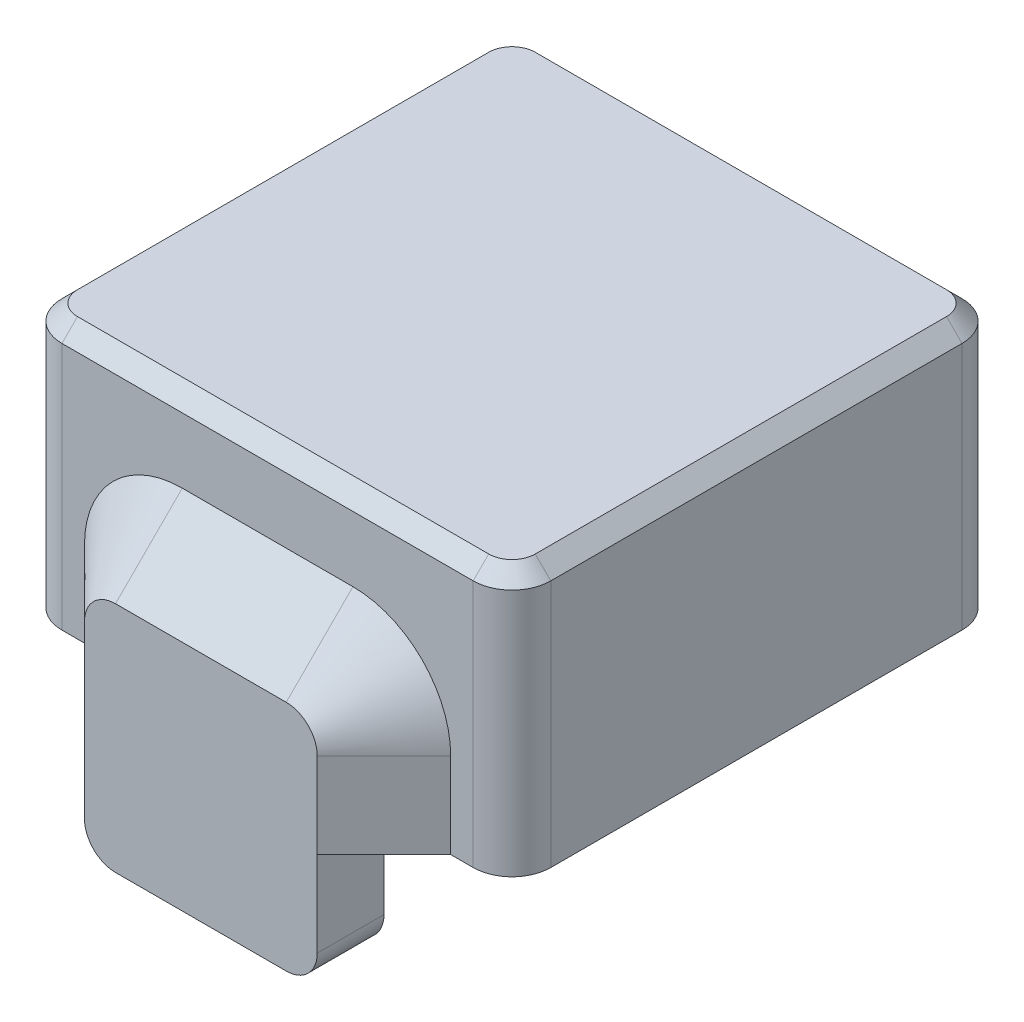
SolidWorks part; units mm, degrees
ref_plane "Front Plane" through (0, 0, 0) normal (0, 0, 1) x (1, 0, 0)
ref_plane "Top Plane" through (0, 0, 0) normal (0, 1, 0) x (1, 0, 0)
ref_plane "Right Plane" through (0, 0, 0) normal (1, 0, 0) x (0, 0, -1)
sketch "Sketch1" plane through (0, 0, 0) normal (0, 1, 0) x (1, 0, 0)
  line L0 (0, 0) -> (-3.15, 0) construction
  line L1 (-3.15, -3.15) -> (3.15, -3.15)
  line L2 (-3.15, -3.15) -> (-3.15, 3.15)
  line L3 (-3.15, 3.15) -> (3.15, 3.15)
  line L4 (3.15, -3.15) -> (3.15, 3.15)
  line L5 (-3.15, -3.15) -> (3.15, 3.15) construction
  line L6 (-3.15, 3.15) -> (3.15, -3.15) construction
  line L7 (-1.5, 3.15) -> (1.5, 3.15)
  line L8 (-1.5, 3.15) -> (-1.5, 4.01)
  line L9 (-1.5, 4.01) -> (1.5, 4.01)
  line L10 (1.5, 3.15) -> (1.5, 4.01)
  line L11 (-1.5, -3.15) -> (-1.5, -4.01)
  line L12 (-1.5, -3.15) -> (1.5, -3.15)
  line L13 (1.5, -3.15) -> (1.5, -4.01)
  line L14 (-1.5, -4.01) -> (1.5, -4.01)
  circle A0 centre (0, 0) radius 1.625
  circle A1 centre (0, 0) radius 1.1
  point P0 (0, 0)
  point P18 (0, 4.01)
  dimension "D2" = 2.2
  dimension "D3" = 3.25
  dimension "D1" = 6.3
  dimension "D4" = 3
  dimension "D5" = 0.86
extrude "Boss-Extrude1" add sketch "Sketch1" along normal blind 3.4 contours L1 L4 L3 L2 A0 | A0 A1 | A1 region at (-3.0609, 0, 0) region at (-1.579, 0, 0) region at (0, 0, 0)
extrude "Cut-Extrude1" cut sketch "Sketch1<3>" along normal blind 2.6 contours A0 A1 region at (-1.579, 0, 0)
sketch "Sketch1<3>" plane through (0, 0, 0) normal (0, 1, 0) x (1, 0, 0) same geometry as "Sketch1"
extrude "Boss-Extrude2" add sketch "Sketch1<4>" along normal mid plane 3 contours L11 L14 L13 L1 | L3 L10 L9 L8 region at (0, 0, 3.58) region at (0, 0, -3.58)
sketch "Sketch1<4>" plane through (0, 0, 0) normal (0, 1, 0) x (1, 0, 0) same geometry as "Sketch1"
fillet "Fillet1" radius 0.4 8 edges at (1.5, 1.5, -3.58) (-1.5, 1.5, -3.58) (1.5, 1.5, 3.58) (-1.5, 1.5, 3.58) (-1.5, -1.5, -3.58) (1.5, -1.5, -3.58) (1.5, -1.5, 3.58) (-1.5, -1.5, 3.58)
chamfer "Chamfer1" distance 0.86 angle 45 10 edges at (-1.5, 0.55, 3.15) (1.5, 0.55, 3.15) (-1.3828, 1.3828, 3.15) (1.3828, 1.3828, 3.15) (0, 1.5, 3.15) (-1.5, 0.55, -3.15) (1.5, 0.55, -3.15) (-1.3828, 1.3828, -3.15) (1.3828, 1.3828, -3.15) (0, 1.5, -3.15)
fillet "Fillet2" radius 0.5 4 edges at (-3.15, 1.7, -3.15) (3.15, 1.7, -3.15) (3.15, 1.7, 3.15) (-3.15, 1.7, 3.15)
extrude "Cut-Extrude2" cut sketch "Sketch1<5>" along normal blind 2.9599 contours A1 region at (0, 0, 0)
sketch "Sketch1<5>" plane through (0, 0, 0) normal (0, 1, 0) x (1, 0, 0) same geometry as "Sketch1"
chamfer "Chamfer2" distance 0.2 angle 45 8 edges at (3.0036, 3.4, -3.0036) (3.15, 3.4, 0) (3.0036, 3.4, 3.0036) (0, 3.4, 3.15) (-3.0036, 3.4, 3.0036) (-3.15, 3.4, 0) (-3.0036, 3.4, -3.0036) (0, 3.4, -3.15)
